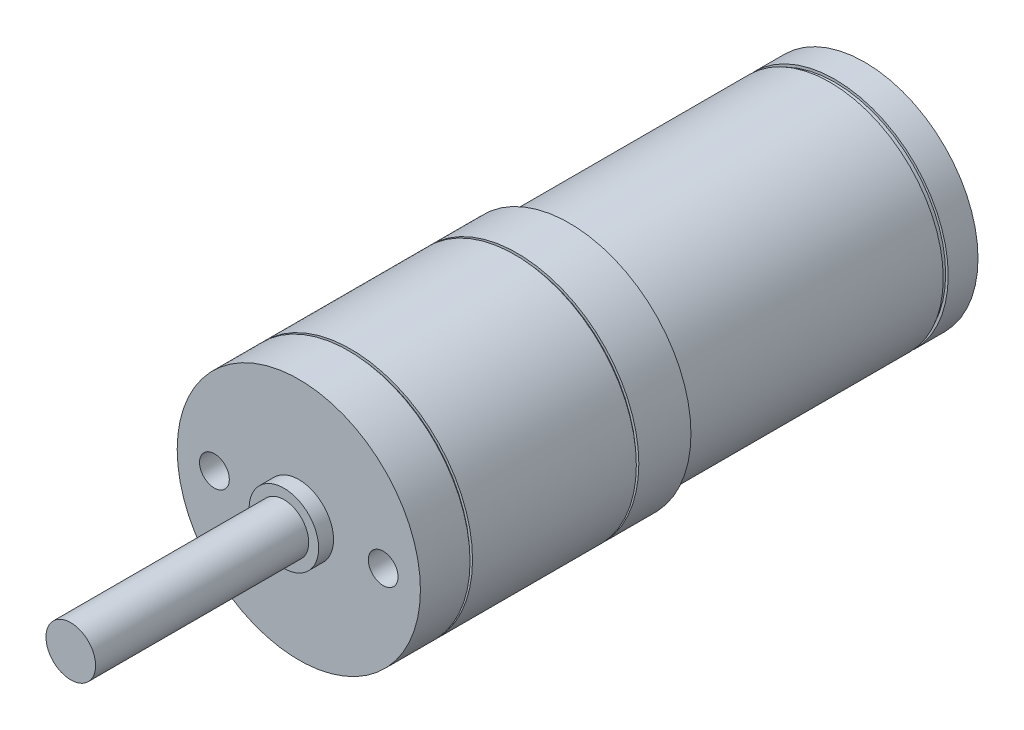
SolidWorks part; units mm, degrees
material "AISI 304"
ref_plane "Front Plane" through (0, 0, 0) normal (0, 0, 1) x (1, 0, 0)
ref_plane "Top Plane" through (0, 0, 0) normal (0, 1, 0) x (1, 0, 0)
ref_plane "Right Plane" through (0, 0, 0) normal (1, 0, 0) x (0, 0, -1)
sketch "Sketch1" plane through (0, 0, 0) normal (0, 0, 1) x (1, 0, 0)
  circle A0 centre (0, 0) radius 12.25
  dimension "D1" = 24.5
extrude "Boss-Extrude1" add sketch "Sketch1" against normal blind 27
sketch "Sketch2" plane through (0, 0, -27) normal (0, 0, -1) x (-1, 0, 0)
  circle A0 centre (0, 0) radius 11.4144
extrude "Boss-Extrude2" add sketch "Sketch2" along normal blind 30
sketch "Sketch3" plane through (0, 0, 0) normal (0, 0, 1) x (1, 0, 0)
  circle A0 centre (0, 0) radius 2.5
  dimension "D1" = 5
extrude "Boss-Extrude3" add sketch "Sketch3" along normal blind 9.4
sketch "Sketch4" plane through (0, 0, 0) normal (1, 0, 0) x (0, 0, -1)
  line L0 (59.6688, -6) -> (55.6565, -6) construction
  line L1 (59.6688, -7.1314) -> (55.6565, -7.1314)
  line L2 (59.6688, -4.8686) -> (55.6565, -4.8686)
  line L3 (57, 0) -> (62.3672, 0) construction
  line L4 (57, -11.4144) -> (57, 11.4144) construction
  line L5 (59.6688, 6) -> (55.6565, 6) construction
  line L6 (59.6688, 7.1314) -> (55.6565, 7.1314)
  line L7 (59.6688, 4.8686) -> (55.6565, 4.8686)
  arc A0 (59.6688, -7.1314) -> (59.6688, -4.8686) centre (59.6688, -6) ccw
  arc A1 (55.6565, -4.8686) -> (55.6565, -7.1314) centre (55.6565, -6) ccw
  arc A2 (59.6688, 7.1314) -> (59.6688, 4.8686) centre (59.6688, 6) cw
  arc A3 (55.6565, 4.8686) -> (55.6565, 7.1314) centre (55.6565, 6) cw
  point P2 (57.6626, -6)
  point P16 (57.6626, 6)
  dimension "D1" = 12
extrude "Boss-Extrude4" add sketch "Sketch4" along normal mid plane 2
sketch "Sketch5" plane through (-1, 0, 0) normal (-1, 0, 0) x (0, 0, 1)
  circle A0 centre (-59.6688, -6) radius 0.5
  circle A1 centre (-59.6688, 6) radius 0.5
  dimension "D1" = 1
  dimension "D2" = 1
extrude "Cut-Extrude1" cut sketch "Sketch5" against normal blind 2
sketch "Sketch6" plane through (0, 0, 0) normal (0, 0, 1) x (1, 0, 0)
  circle A0 centre (0, 0) radius 3.5
  dimension "D1" = 7
extrude "Boss-Extrude5" add sketch "Sketch6" along normal blind 1.5
sketch "Sketch7" plane through (0, 0, -57) normal (0, 0, -1) x (-1, 0, 0)
  circle A0 centre (0, 0) radius 3.1614
extrude "Boss-Extrude6" add sketch "Sketch7" along normal blind 1
fillet "Fillet1" radius 1 1 edges at (-3.1614, 0, -58)
sketch "Sketch8" plane through (0, 0, 9.4) normal (0, 0, 1) x (1, 0, 0)
  line L0 (-1.8427, 1.6895) -> (1.8427, 1.6895)
  circle A0 centre (0, 0) radius 2.5 construction
  arc A1 (1.8427, 1.6895) -> (-1.8427, 1.6895) centre (0, 0) ccw
extrude "Cut-Extrude2" cut sketch "Sketch8" against normal blind 8
sketch "Sketch9" plane through (0, 0, 0) normal (0, 0, 1) x (1, 0, 0)
  line L0 (0, 0) -> (8.5, 0) construction
  line L1 (0, 0) -> (-8.5, 0) construction
  circle A0 centre (-8.5, 0) radius 1.5
  circle A1 centre (8.5, 0) radius 1.5
  dimension "D1" = 3
  dimension "D2" = 3
  dimension "D3" = 8.5
  dimension "D4" = 8.5
extrude "Cut-Extrude3" cut sketch "Sketch9" against normal blind 6
ref_plane "Plane1" through (0, 0, -5) normal (0, 0, 1) x (1, 0, 0)
sketch "Sketch10" plane through (0, 0, -5) normal (0, 0, 1) x (1, 0, 0)
  circle A0 centre (0, 0) radius 12.25 construction
  circle A1 centre (0, 0) radius 12.25
  circle A2 centre (0, 0) radius 11.9752
extrude "Cut-Extrude4" cut sketch "Sketch10" against normal blind 0.25
ref_plane "Plane2" through (0, 0, -13.5) normal (0, 0, 1) x (1, 0, 0)
mirror "Mirror1" about plane through (0, 0, -13.5) normal (0, 0, 1) of "Cut-Extrude4"
ref_plane "Plane3" through (0, 0, -27.25) normal (0, 0, -1) x (-1, 0, 0)
sketch "Sketch11" plane through (0, 0, -27.25) normal (0, 0, -1) x (-1, 0, 0)
  circle A0 centre (0, 0) radius 11.4144 construction
  circle A1 centre (0, 0) radius 11.4144
extrude "Cut-Extrude7" cut sketch "Sketch11" against normal blind 0.5
fillet "Fillet2" radius 0.5 1 edges at (-11.4144, 0, -27.25)
sketch "Sketch12" plane through (0, 0, -27) normal (0, 0, -1) x (-1, 0, 0)
  circle A1 centre (0, 0) radius 12.25
  circle A2 centre (0, 0) radius 12.25
  dimension "D1" = 0
extrude "Boss-Extrude7" add sketch "Sketch12" along normal up to surface (0.25 mm away) up to face at (-10.9144, 0, -27.25)
ref_plane "Plane4" through (0, 0, -54) normal (0, 0, -1) x (-1, 0, 0)
sketch "Sketch13" plane through (0, 0, -54) normal (0, 0, -1) x (-1, 0, 0)
  circle A0 centre (0, 0) radius 11.4144 construction
  circle A1 centre (0, 0) radius 11.4144
  circle A2 centre (0, 0) radius 11.1544
extrude "Cut-Extrude8" cut sketch "Sketch13" against normal blind 0.5
sketch "Sketch14" plane through (0, 0, 9.4) normal (0, 0, 1) x (1, 0, 0)
extrude "Boss-Extrude8" add sketch "Sketch3<2>" along normal blind 22.9697
sketch "Sketch3<2>" plane through (0, 0, 0) normal (0, 0, 1) x (1, 0, 0) same geometry as "Sketch3"
